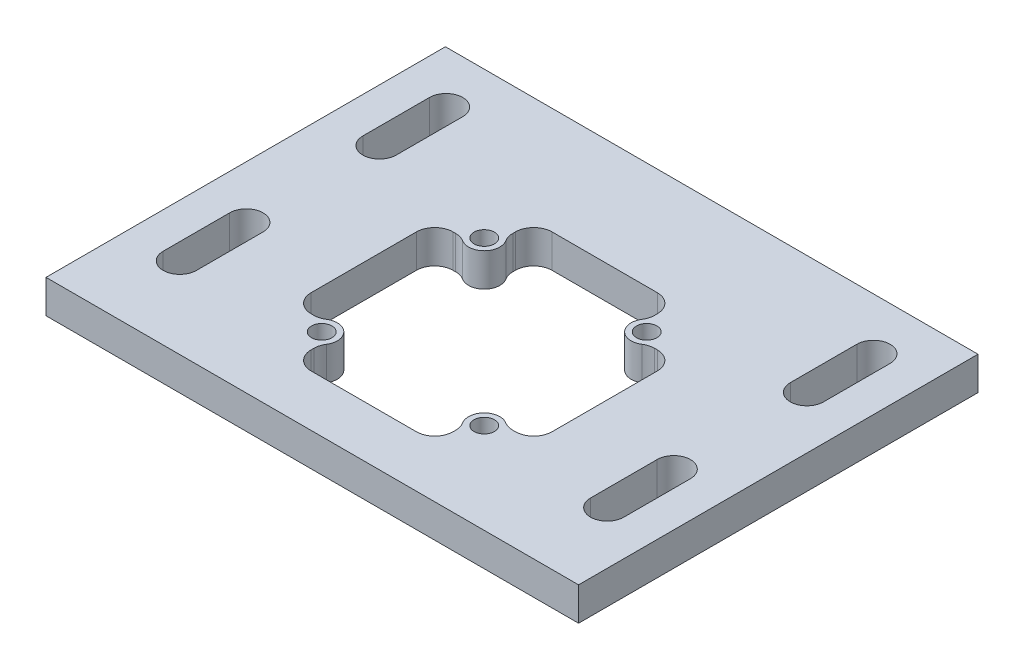
SolidWorks part; units mm, degrees
ref_plane "Front Plane" through (0, 0, 0) normal (0, 0, 1) x (1, 0, 0)
ref_plane "Top Plane" through (0, 0, 0) normal (0, 1, 0) x (1, 0, 0)
ref_plane "Right Plane" through (0, 0, 0) normal (1, 0, 0) x (0, 0, -1)
sketch "Sketch1" plane through (0, 0, 0) normal (0, 1, 0) x (1, 0, 0)
  line L1 (-50.8, 38.1) -> (50.8, 38.1)
  line L2 (-50.8, 38.1) -> (-50.8, -38.1)
  line L3 (-50.8, -38.1) -> (50.8, -38.1)
  line L4 (50.8, 38.1) -> (50.8, -38.1)
  line L5 (-50.8, 38.1) -> (50.8, -38.1) construction
  line L6 (-50.8, -38.1) -> (50.8, 38.1) construction
  point P0 (0, 0)
  dimension "D1" = 101.6
  dimension "D2" = 76.2
extrude "Boss-Extrude1" add sketch "Sketch1" along normal mid plane 6.35
sketch "Sketch16" plane through (0, 3.175, 0) normal (0, 1, 0) x (1, 0, 0)
  line L0 (50.8, 38.1) -> (-50.8, 38.1) construction
  line L1 (-50.8, 38.1) -> (-50.8, -38.1) construction
  line L2 (0, -3.4925) -> (0, 3.4925) construction
  point P0 (-30, 12.7)
  point P10 (30, 12.7)
  dimension "D1" = 25.4
  dimension "D2" = 20.8
sketch "Sketch25" plane through (0, 3.175, 0) normal (0, 1, 0) x (1, 0, 0)
  line L0 (50.8, 38.1) -> (-50.8, 38.1) construction
  line L2 (-43.942, 28.194) -> (-43.942, 15.494)
  line L4 (-37.592, 28.194) -> (-37.592, 15.494)
  line L6 (-43.942, -9.906) -> (-43.942, -22.606)
  line L8 (-37.592, -9.906) -> (-37.592, -22.606)
  arc A0 (-43.942, 28.194) -> (-37.592, 28.194) centre (-40.767, 28.194) cw
  arc A1 (-37.592, 15.494) -> (-43.942, 15.494) centre (-40.767, 15.494) cw
  arc A2 (-37.592, -9.906) -> (-43.942, -9.906) centre (-40.767, -9.906) ccw
  arc A3 (-37.592, -22.606) -> (-43.942, -22.606) centre (-40.767, -22.606) cw
  point P0 (-40.767, 21.844)
  point P1 (-40.767, -16.256)
  point P15 (0, 0)
  point P18 (0, 0)
  point P19 (-43.942, 21.844)
  point P20 (0, 0)
  point P21 (-43.942, -16.256)
  dimension "D5" = 3.175
  dimension "D6" = 3.175
  dimension "D1" = 40.767
  dimension "D2" = 38.1
  dimension "D3" = 12.7
  dimension "D4" = 12.7
  dimension "D7" = 16.256
sketch "Sketch17" plane through (0, 3.175, 0) normal (0, 1, 0) x (1, 0, 0)
  line L0 (-30, 12.7) -> (30, 12.7) construction
  line L1 (-21, -26.3) -> (21, -26.3) construction
  line L2 (-21, -26.3) -> (-21, 15.7) construction
  line L3 (-21, 15.7) -> (21, 15.7) construction
  line L4 (21, -26.3) -> (21, 15.7) construction
  line L5 (-21, -26.3) -> (21, 15.7) construction
  line L6 (-21, 15.7) -> (21, -26.3) construction
  line L7 (-15.5, -20.8) -> (15.5, -20.8) construction
  line L8 (-15.5, -20.8) -> (-15.5, 10.2) construction
  line L9 (-15.5, 10.2) -> (15.5, 10.2) construction
  line L10 (15.5, -20.8) -> (15.5, 10.2) construction
  line L11 (-15.5, -20.8) -> (15.5, 10.2) construction
  line L12 (-15.5, 10.2) -> (15.5, -20.8) construction
  point P0 (0, -5.3)
  point P5 (0, -5.3)
  point P10 (0, 12.7)
  dimension "D1" = 31
  dimension "D2" = 42
  dimension "D3" = 18
hole_wizard "M3.5 Clearance Hole1" positions "Sketch19" profile "Sketch20" hole size "M3.5" standard "ANSI Metric" end condition through all
sketch "Sketch19" plane through (0, 3.175, 0) normal (0, 1, 0) x (1, 0, 0)
  point P0 (-15.5, 10.2)
  point P3 (15.5, 10.2)
  point P6 (15.5, -20.8)
  point P9 (-15.5, -20.8)
sketch "Sketch20" plane through (-15.5, 3.175, -10.2) normal (1, 0, 0) x (0, 0, 1)
  line L0 (0, 0) -> (0, 6.35)
  line L1 (0, 6.35) -> (1.95, 6.35)
  line L2 (1.95, 6.35) -> (1.95, 0)
  line L5 (1.95, 0) -> (0, 0)
  line L11 (0, -6.35) -> (0, 107.95) construction
  dimension "Thru Hole Dia." = 3.9
  dimension "Thru Hole Depth" = 6.35
sketch "Sketch21" plane through (0, 3.175, 0) normal (0, 1, 0) x (1, 0, 0)
  line L0 (-12.9661, 15.7) -> (-12.9661, 11.806) construction
  line L1 (-12.9661, 15.7) -> (12.9661, 15.7) construction
  line L2 (-21, 7.6661) -> (-21, -18.2661) construction
  line L3 (-12.9661, -26.3) -> (12.9661, -26.3) construction
  line L4 (21, 7.6661) -> (21, -18.2661) construction
  line L5 (-15.5, 10.2) -> (15.5, -20.8) construction
  line L7 (12.9661, 15.7) -> (12.9661, 11.806) construction
  line L9 (-21, -18.2661) -> (-17.106, -18.2661) construction
  line L11 (12.9661, -26.3) -> (12.9661, -22.406) construction
  line L13 (-21, -26.3) -> (-21, 15.7) construction
  line L16 (-21, -26.3) -> (21, -26.3) construction
  line L18 (-21, 15.7) -> (21, 15.7) construction
  line L19 (21, -26.3) -> (21, 15.7) construction
  line L22 (-17.106, 7.6661) -> (-21, 7.6661) construction
  line L23 (-44.1452, 24.0875) -> (-44.1452, 20.9125) construction
  line L24 (17.106, 7.6661) -> (21, 7.6661) construction
  line L25 (17.106, -18.2661) -> (21, -18.2661) construction
  line L26 (-12.9661, -22.406) -> (-12.9661, -26.3) construction
  arc A0 (-17.106, 7.6661) -> (-12.9661, 11.806) centre (-15.5, 10.2) ccw construction
  arc A1 (12.9661, 11.806) -> (17.106, 7.6661) centre (15.5, 10.2) ccw construction
  arc A2 (17.106, -18.2661) -> (12.9661, -22.406) centre (15.5, -20.8) ccw construction
  arc A3 (-12.9661, -22.406) -> (-17.106, -18.2661) centre (-15.5, -20.8) ccw construction
  point P4 (0, -5.3)
  point P13 (0, -5.3)
  dimension "D2" = 6
  dimension "D1" = 3.894
sketch "Sketch23" plane through (0, 3.175, 0) normal (0, 1, 0) x (1, 0, 0)
  line L0 (-12.9861, 15.72) -> (-12.9861, 11.8002)
  line L1 (-12.9861, 15.72) -> (12.9861, 15.72)
  line L2 (-21.02, 7.6861) -> (-21.02, -18.2861)
  line L3 (-12.9861, -26.32) -> (12.9861, -26.32)
  line L4 (21.02, 7.6861) -> (21.02, -18.2861)
  line L5 (12.9861, 15.72) -> (12.9861, 11.8002)
  line L6 (-21.02, -18.2861) -> (-17.1002, -18.2861)
  line L7 (12.9861, -26.32) -> (12.9861, -22.4002)
  line L8 (-17.1002, 7.6861) -> (-21.02, 7.6861)
  line L9 (17.1002, 7.6861) -> (21.02, 7.6861)
  line L10 (17.1002, -18.2861) -> (21.02, -18.2861)
  line L11 (-12.9861, -22.4002) -> (-12.9861, -26.32)
  line L16 (21, 7.6661) -> (21, -18.2661) construction
  line L19 (-12.9661, 15.7) -> (12.9661, 15.7) construction
  line L20 (12.9661, 15.7) -> (12.9661, 11.806) construction
  arc A0 (-17.1002, 7.6861) -> (-12.9861, 11.8002) centre (-15.5, 10.2) ccw
  arc A1 (12.9861, 11.8002) -> (17.1002, 7.6861) centre (15.5, 10.2) ccw
  arc A2 (17.1002, -18.2861) -> (12.9861, -22.4002) centre (15.5, -20.8) ccw
  arc A3 (-12.9861, -22.4002) -> (-17.1002, -18.2861) centre (-15.5, -20.8) ccw
  arc A4 (12.9661, 11.806) -> (17.106, 7.6661) centre (15.5, 10.2) ccw construction
  circle A5 centre (-15.5, 10.2) radius 1.95 construction
  dimension "D2" = 0.02
  dimension "D1" = 0.02
  dimension "D4" = 0.02
  dimension "D5" = 0.02
extrude "Cut-Extrude6" cut sketch "Sketch23" against normal through all
sketch "Sketch24" plane through (0, 3.175, 0) normal (0, 1, 0) x (1, 0, 0)
  line L0 (-18.9796, 8.2335) -> (-19.4796, 8.2335)
  line L1 (-22.9796, 4.7335) -> (-22.9796, -15.3335)
  line L2 (-19.4796, -18.8335) -> (-18.9796, -18.8335)
  line L4 (-15.5, 10.2) -> (15.5, -20.8) construction
  line L5 (-12.9861, 11.8002) -> (-7.9861, 11.8002)
  line L6 (-7.9861, 11.8002) -> (-7.9861, -22.4002)
  line L7 (-7.9861, -22.4002) -> (-12.9861, -22.4002)
  arc A0 (-17.1002, 7.6861) -> (-18.9796, 8.2335) centre (-18.9796, 4.7335) ccw
  arc A1 (-17.1002, 7.6861) -> (-12.9861, 11.8002) centre (-15.5, 10.2) ccw construction
  arc A3 (-19.4796, 8.2335) -> (-22.9796, 4.7335) centre (-19.4796, 4.7335) ccw
  arc A7 (-18.9796, -18.8335) -> (-17.1002, -18.2861) centre (-18.9796, -15.3335) ccw
  arc A8 (-22.9796, -15.3335) -> (-19.4796, -18.8335) centre (-19.4796, -15.3335) ccw
  arc A9 (-17.1002, 7.6861) -> (-12.9861, 11.8002) centre (-15.5, 10.2) ccw
  arc A10 (-12.9861, -22.4002) -> (-17.1002, -18.2861) centre (-15.5, -20.8) ccw construction
  arc A11 (-12.9861, -22.4002) -> (-17.1002, -18.2861) centre (-15.5, -20.8) ccw
  point P9 (0, -5.3)
  dimension "D3" = 5
  dimension "D4" = 3.5
  dimension "D5" = 0.5
extrude "Cut-Extrude7" cut sketch "Sketch24" against normal through all
ref_axis "Axis1" through (0, 3.175, 5.3) along (0, 1, 0)
pattern_circular "CirPattern1" count 4 over 360 about axis through (0, 3.175, 5.3) along (0, 1, 0) of "Cut-Extrude7"
extrude "Cut-Extrude8" cut sketch "Sketch25" against normal through all
mirror "Mirror1" about plane through (0, 0, 0) normal (1, 0, 0) of "Cut-Extrude8"
